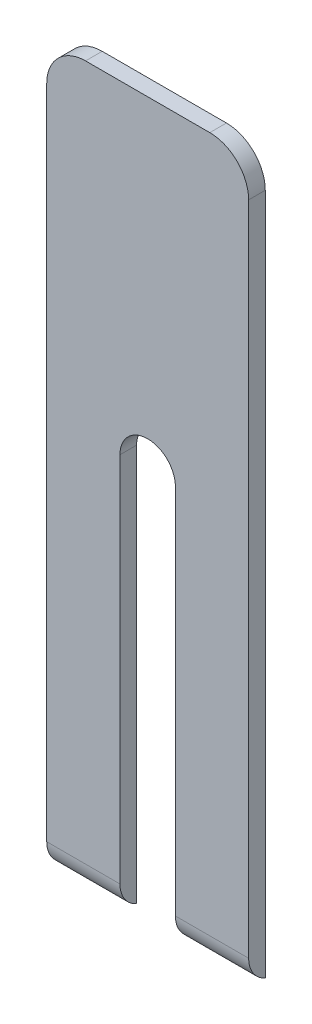
SolidWorks part; units mm, degrees
ref_plane "前视基准面" through (0, 0, 0) normal (0, 0, 1) x (1, 0, 0)
ref_plane "上视基准面" through (0, 0, 0) normal (0, 1, 0) x (1, 0, 0)
ref_plane "右视基准面" through (0, 0, 0) normal (1, 0, 0) x (0, 0, -1)
sketch "草图1" plane through (0, 0, 0) normal (0, 0, 1) x (1, 0, 0)
  line L0 (1.82, 13) -> (1.82, 0) construction
  line L1 (0, 0) -> (3.64, 0) construction
  line L2 (0, 0) -> (0, 12.3)
  line L3 (0.7, 13) -> (2.94, 13)
  line L4 (3.64, 0) -> (3.64, 12.3)
  line L5 (0, 0) -> (1.32, 0)
  line L6 (1.32, 0) -> (1.32, 7.16)
  line L7 (3.64, 0) -> (2.32, 0)
  line L8 (2.32, 0) -> (2.32, 7.16)
  arc A0 (1.32, 7.16) -> (2.32, 7.16) centre (1.82, 7.16) cw
  arc A1 (2.94, 13) -> (3.64, 12.3) centre (2.94, 12.3) cw
  arc A2 (0, 12.3) -> (0.7, 13) centre (0.7, 12.3) cw
  point P15 (3.64, 13)
  dimension "D4" = 1
  dimension "D5" = 0.7
  dimension "D1" = 3.64
  dimension "D2" = 13
  dimension "D3" = 7.16
extrude "凸台-拉伸1" add sketch "草图1" along normal blind 0.3
fillet "圆角1" radius 0.5 2 edges at (0.66, 0, 0.3) (2.98, 0, 0.3)
